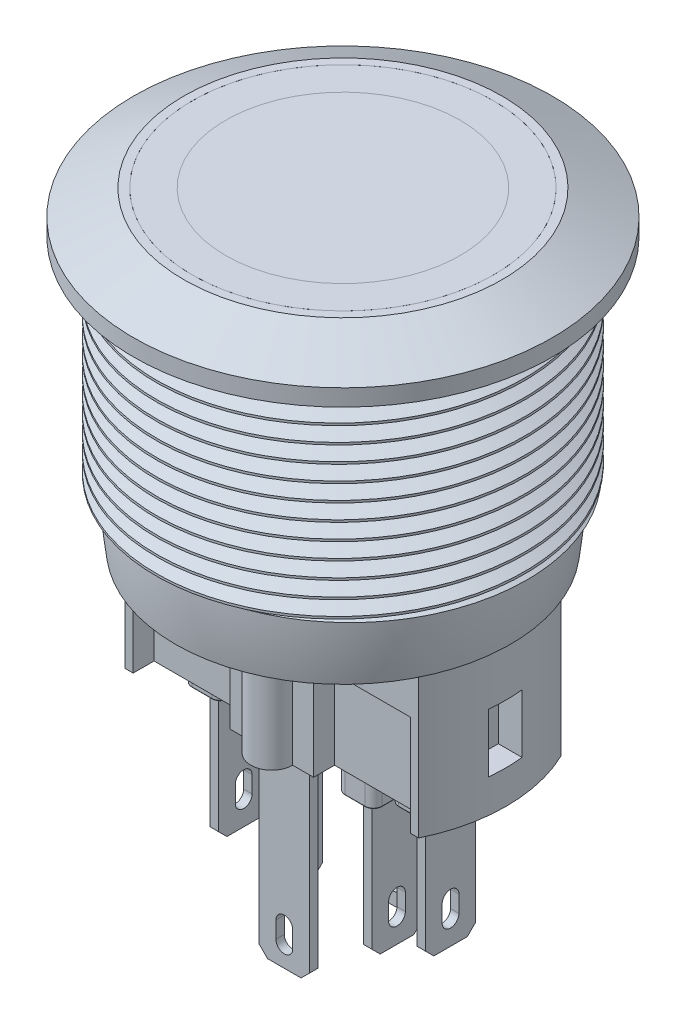
SolidWorks part; units mm, degrees
ref_plane "Ön Düzlem" through (0, 0, 0) normal (0, 0, 1) x (1, 0, 0)
ref_plane "Üst Düzlem" through (0, 0, 0) normal (0, 1, 0) x (1, 0, 0)
ref_plane "Sağ Düzlem" through (0, 0, 0) normal (1, 0, 0) x (0, 0, -1)
sketch "Çizim1" plane through (0, 0, 0) normal (0, 0, 1) x (1, 0, 0)
  line L1 (-11, 3.5267) -> (-11, 16.1)
  line L2 (-11, 16.1) -> (-12.5, 16.1)
  line L3 (-12.5, 16.1) -> (-12.5, 17.1)
  line L6 (0, 17.6) -> (0, 3.5267)
  line L7 (-9, 18.6) -> (-9, 17.6)
  line L8 (-9, 17.6) -> (0, 17.6)
  line L9 (0, 3.5267) -> (-10, 3.5267)
  line L10 (-10, 0) -> (-9.7474, 0)
  line L11 (-10.25, 3.5267) -> (-11, 3.5267)
  line L12 (-9.7474, 0) -> (0, 0) construction
  line L13 (-9, 18.6) -> (-9.5, 18.6)
  line L14 (-9.5, 18.6) -> (-12.5, 17.1)
  line L15 (0, 3.5267) -> (0, 0) construction
  arc A0 (-10.25, 3.5267) -> (-10, 0) centre (14.75, 3.5267) ccw
  arc A1 (-10, 3.5267) -> (-9.7474, 0) centre (14.75, 3.5267) ccw
  arc A2 (-10, 3.5267) -> (-9.7525, 0.0353) centre (14.75, 3.5267) ccw construction
  dimension "D9" = 25
  dimension "D1" = 11
  dimension "D2" = 3.5
  dimension "D3" = 1.5
  dimension "D4" = 1
  dimension "D5" = 1
  dimension "D6" = 2.5
  dimension "D7" = 10
  dimension "D8" = 10.25
  dimension "D11" = 10
  dimension "D12" = 18.6
  dimension "D13" = 0.5
  dimension "D10" = 0.25
revolve "Döndür1" add sketch "Çizim1" angle 360 about L15
sketch "Çizim2" plane through (0, 0, 0) normal (0, 0, 1) x (1, 0, 0)
  line L0 (-10, 3.5267) -> (10, 3.5267) construction
  line L1 (-11, 3.5267) -> (11, 3.5267) construction
  line L2 (-9.7474, 0) -> (9.7474, 0) construction
  line L3 (-10.25, 3.5267) -> (10.25, 3.5267) construction
  line L4 (10, 3.5267) -> (0, 3.5267)
  line L5 (0, 3.5267) -> (0, 0.5)
  line L6 (0, 0.5) -> (9.8051, 0.5)
  arc A0 (10, 3.5267) -> (9.8051, 0.5) centre (-24.9923, 4.2602) cw
  dimension "D1" = 35
  dimension "D2" = 0.5
  dimension "D3" = 10
  dimension "D4" = 3.0267
revolve "Döndür2" add sketch "Çizim2" angle 360 about L5
sketch "Çizim3" plane through (0, 0.5, 0) normal (0, -1, 0) x (1, 0, 0)
  line L0 (0, -4.25) -> (0, 4.25) construction
  line L1 (-8.775, 4.25) -> (-1.25, 4.25)
  line L2 (-8.775, -4.25) -> (-1.25, -4.25)
  line L3 (1.25, 4.25) -> (8.775, 4.25)
  line L4 (1.25, -4.25) -> (8.775, -4.25)
  arc A0 (-8.775, 4.25) -> (-8.775, -4.25) centre (0, 0) ccw
  arc A1 (8.775, -4.25) -> (8.775, 4.25) centre (0, 0) ccw
  circle A2 centre (0, 0) radius 5.5 construction
  arc A3 (1.25, 4.25) -> (-1.25, 4.25) centre (0, 4.25) ccw
  arc A4 (-1.25, -4.25) -> (1.25, -4.25) centre (0, -4.25) ccw
  point P6 (0, 0)
  point P9 (0, 4.25)
  point P12 (0, -4.25)
  dimension "D1" = 19.5
  dimension "D3" = 11
  dimension "D2" = 8.5
  dimension "D4" = 7.525
extrude "Yükseklik-Ekstrüzyon1" add sketch "Çizim3" along normal blind 9
sketch "Çizim5" plane through (0, -8.5, 0) normal (0, -1, 0) x (1, 0, 0)
  line L0 (-1.25, 4.25) -> (-8.775, 4.25) construction
  line L1 (-2.5, -3) -> (-1.5, -3)
  line L2 (-8.275, -3) -> (-8.275, 3)
  line L3 (-2.5, 3) -> (-1.5, 3)
  line L4 (8.275, -3) -> (8.275, 3)
  line L5 (-8.275, -3) -> (8.275, 3) construction
  line L6 (-8.275, 3) -> (8.275, -3) construction
  line L8 (-8.275, 3) -> (-8.275, 4.25)
  line L9 (-8.275, 4.25) -> (-2.5, 4.25)
  line L10 (-2.5, 3) -> (-2.5, 4.25)
  line L11 (8.775, 4.25) -> (1.25, 4.25) construction
  line L13 (2.5, 3) -> (2.5, 4.25)
  line L14 (2.5, 4.25) -> (8.275, 4.25)
  line L15 (8.275, 3) -> (8.275, 4.25)
  line L16 (0, 5.5) -> (0, 3) construction
  line L17 (2.5, 4.25) -> (-2.5, 4.25) construction
  line L18 (0, 0) -> (1.3284, 0) construction
  line L19 (-8.275, -4.25) -> (-2.5, -4.25)
  line L20 (-2.5, -3) -> (-2.5, -4.25)
  line L22 (-8.275, -3) -> (-8.275, -4.25)
  line L23 (2.5, -4.25) -> (8.275, -4.25)
  line L24 (8.275, -3) -> (8.275, -4.25)
  line L26 (2.5, -3) -> (2.5, -4.25)
  line L27 (1.5, 3) -> (2.5, 3)
  line L29 (-1.5, 3) -> (-1.5, 3.5)
  line L30 (-1.5, 3.5) -> (1.5, 3.5)
  line L31 (1.5, 3) -> (1.5, 3.5)
  line L32 (1.5, -3) -> (2.5, -3)
  line L33 (1.5, 3) -> (-1.5, 3) construction
  line L34 (-1.5, -3.5) -> (1.5, -3.5)
  line L35 (-1.5, -3.5) -> (-1.5, -3)
  line L37 (1.5, -3.5) -> (1.5, -3)
  arc A0 (1.25, 4.25) -> (-1.25, 4.25) centre (0, 4.25) ccw construction
  point P0 (0, 0)
  point P25 (0, 4.25)
  point P36 (0, -3)
  point P39 (0, 3)
  dimension "D1" = 5
  dimension "D2" = 6
  dimension "D3" = 0.5
  dimension "D4" = 0.5
  dimension "D5" = 3
extrude "Kes-Ekstrüzyon1" cut sketch "Çizim5" against normal offset from surface (6 mm away) 3 up to face at (0, 0.5, 0)
sketch "Çizim6" plane through (0, 0, 0) normal (1, 0, 0) x (0, 0, -1)
  line L1 (-1, -6.5) -> (1, -6.5)
  line L2 (-1, -6.5) -> (-1, -3)
  line L3 (-1, -3) -> (1, -3)
  line L4 (1, -6.5) -> (1, -3)
  dimension "D1" = 1
  dimension "D2" = 1
  dimension "D3" = 3
  dimension "D4" = 3.5
extrude "Kes-Ekstrüzyon2" cut sketch "Çizim6" against normal through all and the other way through all
sketch "Çizim7" plane through (0, -2.5, 0) normal (0, -1, 0) x (-1, 0, 0)
  line L0 (1.5, -3) -> (2.5, -3) construction
  line L1 (8.275, -3) -> (-8.275, -3)
  line L2 (8.275, -3) -> (8.275, 3)
  line L3 (8.275, 3) -> (-8.275, 3)
  line L4 (-8.275, -3) -> (-8.275, 3)
  line L5 (2.5, 3) -> (1.5, 3) construction
  line L6 (8.275, -4.25) -> (8.275, 4.25) construction
  line L7 (-8.275, 4.25) -> (-8.275, -4.25) construction
extrude "Yükseklik-Ekstrüzyon2" add sketch "Çizim7" along normal up to surface (6 mm away) separate body up to face at (-8.7687, -8.5, 0)
sketch "Çizim8" plane through (0, -8.5, 0) normal (0, -1, 0) x (1, 0, 0)
  line L0 (-6.175, 0) -> (0, 0) construction
  line L1 (-6.775, -2.25) -> (-5.575, -2.25)
  line L2 (-7.275, -1.75) -> (-7.275, 1.75)
  line L3 (-6.775, 2.25) -> (-5.575, 2.25)
  line L4 (-5.075, -1.75) -> (-5.075, 1.75)
  line L5 (-7.275, -2.25) -> (-5.075, 2.25) construction
  line L6 (-7.275, 2.25) -> (-5.075, -2.25) construction
  line L7 (0, 0) -> (0, 2.1485) construction
  line L8 (6.425, -1.5) -> (5.925, -1.5)
  line L9 (-6.425, -1.5) -> (-5.925, -1.5)
  line L10 (-6.425, -1.5) -> (-6.425, 1.5)
  line L11 (-6.425, 1.5) -> (-5.925, 1.5)
  line L12 (-5.925, -1.5) -> (-5.925, 1.5)
  line L13 (-6.425, -1.5) -> (-5.925, 1.5) construction
  line L14 (-6.425, 1.5) -> (-5.925, -1.5) construction
  line L15 (6.425, -1.5) -> (6.425, 1.5)
  line L16 (5.925, -1.5) -> (5.925, 1.5)
  line L17 (6.425, 1.5) -> (5.925, 1.5)
  line L18 (6.775, 2.25) -> (5.575, 2.25)
  line L19 (5.075, -1.75) -> (5.075, 1.75)
  line L20 (6.775, -2.25) -> (5.575, -2.25)
  line L21 (7.275, -1.75) -> (7.275, 1.75)
  line L22 (-8.275, 3) -> (-8.275, -3) construction
  arc A0 (5.075, -1.75) -> (5.575, -2.25) centre (5.575, -1.75) ccw
  arc A1 (6.775, -2.25) -> (7.275, -1.75) centre (6.775, -1.75) ccw
  arc A2 (6.775, 2.25) -> (7.275, 1.75) centre (6.775, 1.75) cw
  arc A3 (5.575, 2.25) -> (5.075, 1.75) centre (5.575, 1.75) ccw
  arc A4 (-6.775, -2.25) -> (-7.275, -1.75) centre (-6.775, -1.75) cw
  arc A5 (-5.575, -2.25) -> (-5.075, -1.75) centre (-5.575, -1.75) ccw
  arc A6 (-5.575, 2.25) -> (-5.075, 1.75) centre (-5.575, 1.75) cw
  arc A7 (-7.275, 1.75) -> (-6.775, 2.25) centre (-6.775, 1.75) cw
  point P0 (-6.175, 0)
  point P25 (5.075, -2.25)
  point P28 (7.275, -2.25)
  point P31 (7.275, 2.25)
  point P34 (5.075, 2.25)
  dimension "D6" = 0.5
  dimension "D1" = 2.2
  dimension "D2" = 4.5
  dimension "D3" = 0.5
  dimension "D4" = 3
  dimension "D5" = 1
extrude "Yükseklik-Ekstrüzyon3" add sketch "Çizim8" along normal blind 1
sketch "Çizim9" plane through (0, -8.5, 0) normal (0, -1, 0) x (1, 0, 0)
  line L1 (-3.575, -2.25) -> (-2.375, -2.25)
  line L2 (-4.075, -1.75) -> (-4.075, 1.75)
  line L3 (-3.575, 2.25) -> (-2.375, 2.25)
  line L4 (-1.875, -1.75) -> (-1.875, 1.75)
  line L5 (-4.075, -2.25) -> (-1.875, 2.25) construction
  line L6 (-4.075, 2.25) -> (-1.875, -2.25) construction
  line L7 (-5.575, 2.25) -> (-6.775, 2.25) construction
  line L8 (-6.775, -2.25) -> (-5.575, -2.25) construction
  line L9 (-5.925, 1.5) -> (-6.425, 1.5) construction
  line L10 (-3.225, -1.5) -> (-2.725, -1.5)
  line L11 (-3.225, -1.5) -> (-3.225, 1.5)
  line L12 (-3.225, 1.5) -> (-2.725, 1.5)
  line L13 (-2.725, -1.5) -> (-2.725, 1.5)
  line L14 (-3.225, -1.5) -> (-2.725, 1.5) construction
  line L15 (-3.225, 1.5) -> (-2.725, -1.5) construction
  line L16 (-2.975, 0) -> (0, 0) construction
  line L17 (0, 0) -> (0, 1.2456) construction
  line L18 (3.225, 1.5) -> (2.725, 1.5)
  line L19 (2.725, -1.5) -> (2.725, 1.5)
  line L20 (3.225, -1.5) -> (2.725, -1.5)
  line L21 (3.225, -1.5) -> (3.225, 1.5)
  line L22 (3.575, 2.25) -> (2.375, 2.25)
  line L23 (1.875, -1.75) -> (1.875, 1.75)
  line L24 (3.575, -2.25) -> (2.375, -2.25)
  line L25 (4.075, -1.75) -> (4.075, 1.75)
  line L26 (-5.075, -1.75) -> (-5.075, 1.75) construction
  arc A0 (1.875, -1.75) -> (2.375, -2.25) centre (2.375, -1.75) ccw
  arc A1 (3.575, -2.25) -> (4.075, -1.75) centre (3.575, -1.75) ccw
  arc A2 (3.575, 2.25) -> (4.075, 1.75) centre (3.575, 1.75) cw
  arc A3 (2.375, 2.25) -> (1.875, 1.75) centre (2.375, 1.75) ccw
  arc A4 (-3.575, -2.25) -> (-4.075, -1.75) centre (-3.575, -1.75) cw
  arc A5 (-2.375, -2.25) -> (-1.875, -1.75) centre (-2.375, -1.75) ccw
  arc A6 (-2.375, 2.25) -> (-1.875, 1.75) centre (-2.375, 1.75) cw
  arc A7 (-4.075, 1.75) -> (-3.575, 2.25) centre (-3.575, 1.75) cw
  point P0 (-2.975, 0)
  point P11 (-2.975, 0)
  point P32 (1.875, -2.25)
  point P35 (4.075, -2.25)
  point P38 (4.075, 2.25)
  point P41 (1.875, 2.25)
  dimension "D4" = 0.5
  dimension "D1" = 1
  dimension "D2" = 2.2
  dimension "D3" = 0.5
extrude "Yükseklik-Ekstrüzyon4" add sketch "Çizim9" along normal offset from surface (2 mm away) 1 up to face at (-6.175, -9.5, 0) offset beyond the face yes
sketch "Çizim10" plane through (0, -9.5, 0) normal (0, -1, 0) x (1, 0, 0)
  line L0 (-6.775, -2.15) -> (-5.575, -2.15)
  line L1 (-5.175, -1.75) -> (-5.175, 1.75)
  line L2 (-5.575, 2.15) -> (-6.775, 2.15)
  line L3 (-7.175, 1.75) -> (-7.175, -1.75)
  line L4 (-6.775, -2.25) -> (-5.575, -2.25)
  line L5 (-5.075, -1.75) -> (-5.075, 1.75)
  line L6 (-5.575, 2.25) -> (-6.775, 2.25)
  line L7 (-7.275, 1.75) -> (-7.275, -1.75)
  line L8 (-6.775, -2.25) -> (-5.575, -2.25) construction
  line L9 (-5.075, -1.75) -> (-5.075, 1.75) construction
  line L10 (-5.575, 2.25) -> (-6.775, 2.25) construction
  line L11 (-7.275, 1.75) -> (-7.275, -1.75) construction
  line L12 (5.575, -2.25) -> (6.775, -2.25)
  line L13 (7.275, -1.75) -> (7.275, 1.75)
  line L14 (6.775, 2.25) -> (5.575, 2.25)
  line L15 (5.075, 1.75) -> (5.075, -1.75)
  line L16 (5.575, -2.25) -> (6.775, -2.25) construction
  line L17 (7.275, -1.75) -> (7.275, 1.75) construction
  line L18 (6.775, 2.25) -> (5.575, 2.25) construction
  line L19 (5.075, 1.75) -> (5.075, -1.75) construction
  line L20 (5.575, -2.15) -> (6.775, -2.15)
  line L21 (7.175, -1.75) -> (7.175, 1.75)
  line L22 (6.775, 2.15) -> (5.575, 2.15)
  line L23 (5.175, 1.75) -> (5.175, -1.75)
  line L25 (-6.425, 1.5) -> (-5.925, 1.5)
  line L26 (-6.425, 1.5) -> (-6.425, -1.5)
  line L27 (-6.425, -1.5) -> (-5.925, -1.5)
  line L28 (-5.925, 1.5) -> (-5.925, -1.5)
  line L29 (5.925, 1.5) -> (6.425, 1.5)
  line L30 (5.925, 1.5) -> (5.925, -1.5)
  line L31 (5.925, -1.5) -> (6.425, -1.5)
  line L32 (6.425, 1.5) -> (6.425, -1.5)
  arc A0 (-5.575, -2.15) -> (-5.175, -1.75) centre (-5.575, -1.75) ccw
  arc A1 (-5.175, 1.75) -> (-5.575, 2.15) centre (-5.575, 1.75) ccw
  arc A2 (-6.775, 2.15) -> (-7.175, 1.75) centre (-6.775, 1.75) ccw
  arc A3 (-7.175, -1.75) -> (-6.775, -2.15) centre (-6.775, -1.75) ccw
  arc A4 (-7.275, -1.75) -> (-6.775, -2.25) centre (-6.775, -1.75) ccw
  arc A5 (-5.575, -2.25) -> (-5.075, -1.75) centre (-5.575, -1.75) ccw
  arc A6 (-5.075, 1.75) -> (-5.575, 2.25) centre (-5.575, 1.75) ccw
  arc A7 (-6.775, 2.25) -> (-7.275, 1.75) centre (-6.775, 1.75) ccw
  arc A8 (-7.275, -1.75) -> (-6.775, -2.25) centre (-6.775, -1.75) ccw construction
  arc A9 (-5.575, -2.25) -> (-5.075, -1.75) centre (-5.575, -1.75) ccw construction
  arc A10 (-5.075, 1.75) -> (-5.575, 2.25) centre (-5.575, 1.75) ccw construction
  arc A11 (-6.775, 2.25) -> (-7.275, 1.75) centre (-6.775, 1.75) ccw construction
  arc A12 (5.075, -1.75) -> (5.575, -2.25) centre (5.575, -1.75) ccw
  arc A13 (6.775, -2.25) -> (7.275, -1.75) centre (6.775, -1.75) ccw
  arc A14 (7.275, 1.75) -> (6.775, 2.25) centre (6.775, 1.75) ccw
  arc A15 (5.575, 2.25) -> (5.075, 1.75) centre (5.575, 1.75) ccw
  arc A16 (5.075, -1.75) -> (5.575, -2.25) centre (5.575, -1.75) ccw construction
  arc A17 (6.775, -2.25) -> (7.275, -1.75) centre (6.775, -1.75) ccw construction
  arc A18 (7.275, 1.75) -> (6.775, 2.25) centre (6.775, 1.75) ccw construction
  arc A19 (5.575, 2.25) -> (5.075, 1.75) centre (5.575, 1.75) ccw construction
  arc A20 (6.775, -2.15) -> (7.175, -1.75) centre (6.775, -1.75) ccw
  arc A21 (7.175, 1.75) -> (6.775, 2.15) centre (6.775, 1.75) ccw
  arc A22 (5.575, 2.15) -> (5.175, 1.75) centre (5.575, 1.75) ccw
  arc A23 (5.175, -1.75) -> (5.575, -2.15) centre (5.575, -1.75) ccw
  dimension "D1" = 0
  dimension "D2" = 0
  dimension "D3" = 0.1
extrude "Kes-Ekstrüzyon3" cut sketch "Çizim10" against normal blind 0.2
sketch "Çizim11" plane through (0, -10.5, 0) normal (0, -1, 0) x (1, 0, 0)
  line L0 (3.225, -1.5) -> (3.225, 1.5) construction
  line L1 (3.225, 1.5) -> (2.725, 1.5) construction
  line L2 (2.725, 1.5) -> (2.725, -1.5) construction
  line L3 (2.725, -1.5) -> (3.225, -1.5) construction
  line L4 (-2.725, -1.5) -> (-2.725, 1.5) construction
  line L5 (-2.725, 1.5) -> (-3.225, 1.5) construction
  line L6 (-3.225, 1.5) -> (-3.225, -1.5) construction
  line L7 (-3.225, -1.5) -> (-2.725, -1.5) construction
  line L8 (3.225, -1.5) -> (3.225, 1.5)
  line L9 (3.225, 1.5) -> (2.725, 1.5)
  line L10 (2.725, 1.5) -> (2.725, -1.5)
  line L11 (2.725, -1.5) -> (3.225, -1.5)
  line L12 (-2.725, -1.5) -> (-2.725, 1.5)
  line L13 (-2.725, 1.5) -> (-3.225, 1.5)
  line L14 (-3.225, 1.5) -> (-3.225, -1.5)
  line L15 (-3.225, -1.5) -> (-2.725, -1.5)
  line L16 (2.375, -2.25) -> (3.575, -2.25) construction
  line L17 (4.075, -1.75) -> (4.075, 1.75) construction
  line L18 (3.575, 2.25) -> (2.375, 2.25) construction
  line L19 (1.875, 1.75) -> (1.875, -1.75) construction
  line L20 (-3.575, -2.25) -> (-2.375, -2.25) construction
  line L21 (-1.875, -1.75) -> (-1.875, 1.75) construction
  line L22 (-2.375, 2.25) -> (-3.575, 2.25) construction
  line L23 (-4.075, 1.75) -> (-4.075, -1.75) construction
  line L24 (2.375, -2.25) -> (3.575, -2.25) construction
  line L25 (4.075, -1.75) -> (4.075, 1.75) construction
  line L26 (3.575, 2.25) -> (2.375, 2.25) construction
  line L27 (1.875, 1.75) -> (1.875, -1.75) construction
  line L28 (-3.575, -2.25) -> (-2.375, -2.25) construction
  line L29 (-1.875, -1.75) -> (-1.875, 1.75) construction
  line L30 (-2.375, 2.25) -> (-3.575, 2.25) construction
  line L31 (-4.075, 1.75) -> (-4.075, -1.75) construction
  line L32 (-3.575, -2.15) -> (-2.375, -2.15)
  line L33 (-1.975, -1.75) -> (-1.975, 1.75)
  line L34 (-2.375, 2.15) -> (-3.575, 2.15)
  line L35 (-3.975, 1.75) -> (-3.975, -1.75)
  line L36 (2.375, -2.15) -> (3.575, -2.15)
  line L37 (3.975, -1.75) -> (3.975, 1.75)
  line L38 (3.575, 2.15) -> (2.375, 2.15)
  line L39 (1.975, 1.75) -> (1.975, -1.75)
  arc A0 (3.575, -2.25) -> (4.075, -1.75) centre (3.575, -1.75) ccw construction
  arc A1 (4.075, 1.75) -> (3.575, 2.25) centre (3.575, 1.75) ccw construction
  arc A2 (2.375, 2.25) -> (1.875, 1.75) centre (2.375, 1.75) ccw construction
  arc A3 (1.875, -1.75) -> (2.375, -2.25) centre (2.375, -1.75) ccw construction
  arc A4 (-2.375, -2.25) -> (-1.875, -1.75) centre (-2.375, -1.75) ccw construction
  arc A5 (-1.875, 1.75) -> (-2.375, 2.25) centre (-2.375, 1.75) ccw construction
  arc A6 (-3.575, 2.25) -> (-4.075, 1.75) centre (-3.575, 1.75) ccw construction
  arc A7 (-4.075, -1.75) -> (-3.575, -2.25) centre (-3.575, -1.75) ccw construction
  arc A8 (3.575, -2.25) -> (4.075, -1.75) centre (3.575, -1.75) ccw construction
  arc A9 (4.075, 1.75) -> (3.575, 2.25) centre (3.575, 1.75) ccw construction
  arc A10 (2.375, 2.25) -> (1.875, 1.75) centre (2.375, 1.75) ccw construction
  arc A11 (1.875, -1.75) -> (2.375, -2.25) centre (2.375, -1.75) ccw construction
  arc A12 (-2.375, -2.25) -> (-1.875, -1.75) centre (-2.375, -1.75) ccw construction
  arc A13 (-1.875, 1.75) -> (-2.375, 2.25) centre (-2.375, 1.75) ccw construction
  arc A14 (-3.575, 2.25) -> (-4.075, 1.75) centre (-3.575, 1.75) ccw construction
  arc A15 (-4.075, -1.75) -> (-3.575, -2.25) centre (-3.575, -1.75) ccw construction
  arc A16 (-2.375, -2.15) -> (-1.975, -1.75) centre (-2.375, -1.75) ccw
  arc A17 (-1.975, 1.75) -> (-2.375, 2.15) centre (-2.375, 1.75) ccw
  arc A18 (-3.575, 2.15) -> (-3.975, 1.75) centre (-3.575, 1.75) ccw
  arc A19 (-3.975, -1.75) -> (-3.575, -2.15) centre (-3.575, -1.75) ccw
  arc A20 (3.575, -2.15) -> (3.975, -1.75) centre (3.575, -1.75) ccw
  arc A21 (3.975, 1.75) -> (3.575, 2.15) centre (3.575, 1.75) ccw
  arc A22 (2.375, 2.15) -> (1.975, 1.75) centre (2.375, 1.75) ccw
  arc A23 (1.975, -1.75) -> (2.375, -2.15) centre (2.375, -1.75) ccw
  dimension "D1" = 0.1
extrude "Kes-Ekstrüzyon4" cut sketch "Çizim11" against normal blind 0.2
fillet "Radyus1" radius 0.05 96 edges at (7.0578, -9.3, 2.0328) (7.175, -9.3, 0) (7.0578, -9.3, -2.0328) (6.175, -9.3, -2.15) (5.2921, -9.3, -2.0328) (5.175, -9.3, 0) (5.2921, -9.3, 2.0328) (3.8578, -10.3, 2.0328) (3.975, -10.3, 0) (3.8578, -10.3, -2.0328) (2.975, -10.3, -2.15) (2.0921, -10.3, -2.0328) (1.975, -10.3, 0) (2.0921, -10.3, 2.0328) (-2.0921, -10.3, 2.0328) (-1.975, -10.3, 0) (-2.0921, -10.3, -2.0328) (-2.975, -10.3, -2.15) (-3.8578, -10.3, -2.0328) (-3.975, -10.3, 0) (-3.8578, -10.3, 2.0328) (-5.2921, -9.3, 2.0328) (-5.175, -9.3, 0) (-5.2921, -9.3, -2.0328) (-6.175, -9.3, -2.15) (-7.0578, -9.3, -2.0328) (-7.175, -9.3, 0) (-7.0578, -9.3, 2.0328) (6.175, -9.3, 2.15) (2.975, -10.3, 2.15) (-2.975, -10.3, 2.15) (-6.175, -9.3, 2.15) (7.1285, -9.5, 2.1036) (7.275, -9.5, 0) (7.1285, -9.5, -2.1036) (6.175, -9.5, -2.25) (5.2214, -9.5, -2.1036) (5.075, -9.5, 0) (5.2214, -9.5, 2.1036) (7.0578, -9.5, 2.0328) (7.175, -9.5, 0) (7.0578, -9.5, -2.0328) (6.175, -9.5, -2.15) (5.2921, -9.5, -2.0328) (5.175, -9.5, 0) (5.2921, -9.5, 2.0328) (2.0214, -10.5, 2.1036) (1.875, -10.5, 0) (2.0214, -10.5, -2.1036) (2.975, -10.5, -2.25) (3.9285, -10.5, -2.1036) (4.075, -10.5, 0) (3.9285, -10.5, 2.1036) (3.8578, -10.5, 2.0328) (3.975, -10.5, 0) (3.8578, -10.5, -2.0328) (2.975, -10.5, -2.15) (2.0921, -10.5, -2.0328) (1.975, -10.5, 0) (2.0921, -10.5, 2.0328) (-3.9285, -10.5, 2.1036) (-4.075, -10.5, 0) (-3.9285, -10.5, -2.1036) (-2.975, -10.5, -2.25) (-2.0214, -10.5, -2.1036) (-1.875, -10.5, 0) (-2.0214, -10.5, 2.1036) (-2.0921, -10.5, 2.0328) (-1.975, -10.5, 0) (-2.0921, -10.5, -2.0328) (-2.975, -10.5, -2.15) (-3.8578, -10.5, -2.0328) (-3.975, -10.5, 0) (-3.8578, -10.5, 2.0328) (-5.2214, -9.5, 2.1036) (-5.075, -9.5, 0) (-5.2214, -9.5, -2.1036) (-6.175, -9.5, -2.25) (-7.1285, -9.5, -2.1036) (-7.275, -9.5, 0) (-7.1285, -9.5, 2.1036) (-5.2921, -9.5, 2.0328) (-5.175, -9.5, 0) (-5.2921, -9.5, -2.0328) (-6.175, -9.5, -2.15) (-7.0578, -9.5, -2.0328) (-7.175, -9.5, 0) (-7.0578, -9.5, 2.0328) (6.175, -9.5, 2.25) (6.175, -9.5, 2.15) (2.975, -10.5, 2.25) (2.975, -10.5, 2.15) (-2.975, -10.5, 2.25) (-2.975, -10.5, 2.15) (-6.175, -9.5, 2.25) (-6.175, -9.5, 2.15)
sketch "Çizim12" plane through (0, -8.5, 0) normal (0, -1, 0) x (1, 0, 0)
  line L4 (-5.925, -1.5) -> (-5.925, 1.5)
  line L5 (-5.925, 1.5) -> (-6.425, 1.5)
  line L6 (-6.425, 1.5) -> (-6.425, -1.5)
  line L7 (-6.425, -1.5) -> (-5.925, -1.5)
  line L8 (-5.925, -1.5) -> (-5.925, 1.5)
  line L9 (-5.925, 1.5) -> (-6.425, 1.5)
  line L10 (-6.425, 1.5) -> (-6.425, -1.5)
  line L11 (-6.425, -1.5) -> (-5.925, -1.5)
  line L12 (6.425, -1.5) -> (6.425, 1.5)
  line L13 (6.425, 1.5) -> (5.925, 1.5)
  line L14 (5.925, 1.5) -> (5.925, -1.5)
  line L15 (5.925, -1.5) -> (6.425, -1.5)
  line L16 (6.425, -1.5) -> (6.425, 1.5)
  line L17 (6.425, 1.5) -> (5.925, 1.5)
  line L18 (5.925, 1.5) -> (5.925, -1.5)
  line L19 (5.925, -1.5) -> (6.425, -1.5)
  dimension "D1" = 0
  dimension "D2" = 0
extrude "Yükseklik-Ekstrüzyon5" add sketch "Çizim12" along normal offset from surface (8.9 mm away) 36 up to face at (-9.5, 18.6, 0)
sketch "Çizim13" plane through (0, 0, 0) normal (1, 0, 0) x (0, 0, -1)
  line L0 (0, -9.45) -> (0, -17.4) construction
  line L5 (1.75, -9.45) -> (-1.75, -9.45) construction
  line L6 (1.5, -17.4) -> (-1.5, -17.4) construction
  line L7 (0, -15.95) -> (0, -14.95) construction
  line L8 (-0.5, -15.95) -> (-0.5, -14.95)
  line L9 (0.5, -15.95) -> (0.5, -14.95)
  arc A0 (-0.5, -15.95) -> (0.5, -15.95) centre (0, -15.95) ccw
  arc A1 (0.5, -14.95) -> (-0.5, -14.95) centre (0, -14.95) ccw
  point P8 (0, -15.45)
  dimension "D1" = 0.5
  dimension "D2" = 1
  dimension "D3" = 6
extrude "Kes-Ekstrüzyon5" cut sketch "Çizim13" against normal through all and the other way through all
sketch "Çizim14" plane through (0, -8.5, 0) normal (0, -1, 0) x (1, 0, 0)
  line L4 (3.225, -1.5) -> (3.225, 1.5)
  line L5 (3.225, 1.5) -> (2.725, 1.5)
  line L6 (2.725, 1.5) -> (2.725, -1.5)
  line L7 (2.725, -1.5) -> (3.225, -1.5)
  line L8 (3.225, -1.5) -> (3.225, 1.5)
  line L9 (3.225, 1.5) -> (2.725, 1.5)
  line L10 (2.725, 1.5) -> (2.725, -1.5)
  line L11 (2.725, -1.5) -> (3.225, -1.5)
  line L12 (-2.725, -1.5) -> (-2.725, 1.5)
  line L13 (-2.725, 1.5) -> (-3.225, 1.5)
  line L14 (-3.225, 1.5) -> (-3.225, -1.5)
  line L15 (-3.225, -1.5) -> (-2.725, -1.5)
  line L16 (-2.725, -1.5) -> (-2.725, 1.5)
  line L17 (-2.725, 1.5) -> (-3.225, 1.5)
  line L18 (-3.225, 1.5) -> (-3.225, -1.5)
  line L19 (-3.225, -1.5) -> (-2.725, -1.5)
  dimension "D1" = 0
  dimension "D2" = 0
extrude "Yükseklik-Ekstrüzyon6" add sketch "Çizim14" along normal offset from surface (10.4 mm away) 37.5 up to face at (-9.5, 18.6, 0)
sketch "Çizim15" plane through (-2.725, 0, 0) normal (1, 0, 0) x (0, 0, -1)
  line L0 (0, -16.45) -> (0, -17.45) construction
  line L1 (0.5, -16.45) -> (0.5, -17.45)
  line L2 (-0.5, -16.45) -> (-0.5, -17.45)
  line L3 (0, -15.95) -> (0, -16.45) construction
  arc A0 (0.5, -16.45) -> (-0.5, -16.45) centre (0, -16.45) ccw
  arc A1 (-0.5, -17.45) -> (0.5, -17.45) centre (0, -17.45) ccw
  point P3 (0, -16.95)
  dimension "D1" = 0.5
  dimension "D2" = 1
  dimension "D3" = 0.5
extrude "Kes-Ekstrüzyon6" cut sketch "Çizim15" against normal up to vertex (0.5 mm away) and the other way up to vertex (5.9499 mm away) up to point (-3.225, -18.9, 1.5) other way up to point (3.225, -10.3, 1.5)
sketch "Çizim16" plane through (0, -2.5, 0) normal (0, -1, 0) x (1, 0, 0)
  line L4 (-1.5, 3) -> (1.5, 3)
  line L5 (1.5, 3) -> (1.5, 3.5)
  line L6 (1.5, 3.5) -> (-1.5, 3.5)
  line L7 (-1.5, 3.5) -> (-1.5, 3)
  line L8 (-1.5, 3) -> (1.5, 3)
  line L9 (1.5, 3) -> (1.5, 3.5)
  line L10 (1.5, 3.5) -> (-1.5, 3.5)
  line L11 (-1.5, 3.5) -> (-1.5, 3)
  line L12 (1.5, -3) -> (-1.5, -3)
  line L13 (-1.5, -3) -> (-1.5, -3.5)
  line L14 (-1.5, -3.5) -> (1.5, -3.5)
  line L15 (1.5, -3.5) -> (1.5, -3)
  line L16 (1.5, -3) -> (-1.5, -3)
  line L17 (-1.5, -3) -> (-1.5, -3.5)
  line L18 (-1.5, -3.5) -> (1.5, -3.5)
  line L19 (1.5, -3.5) -> (1.5, -3)
  dimension "D1" = 0
  dimension "D2" = 0
extrude "Yükseklik-Ekstrüzyon7" add sketch "Çizim16" along normal offset from surface (17.5 mm away) 38.6 up to face at (-9.5, 18.6, 0)
sketch "Çizim18" plane through (0, 0, 3.5) normal (0, 0, 1) x (1, 0, 0)
  line L0 (0, -20) -> (0, -18.75) construction
  line L1 (-1.5, -20) -> (1.5, -20) construction
  line L2 (0, -18.75) -> (0, -17.75) construction
  line L3 (-0.5, -18.75) -> (-0.5, -17.75)
  line L4 (0.5, -18.75) -> (0.5, -17.75)
  arc A0 (-0.5, -18.75) -> (0.5, -18.75) centre (0, -18.75) ccw
  arc A1 (0.5, -17.75) -> (-0.5, -17.75) centre (0, -17.75) ccw
  point P5 (0, -18.25)
  dimension "D2" = 0.5
  dimension "D1" = 1.25
  dimension "D3" = 1
extrude "Kes-Ekstrüzyon7" cut sketch "Çizim18" against normal up to vertex (7 mm away) up to point (-1.5, -20, -3.5)
chamfer "Pah1" distance 0.5 angle 45 12 edges at (-1.5, -20, 3.25) (1.5, -20, 3.25) (6.175, -17.4, 1.5) (6.175, -17.4, -1.5) (2.975, -18.9, 1.5) (2.975, -18.9, -1.5) (-2.975, -18.9, -1.5) (-2.975, -18.9, 1.5) (-6.175, -17.4, 1.5) (-6.175, -17.4, -1.5) (-1.5, -20, -3.25) (1.5, -20, -3.25)
sketch "Çizim19" plane through (0, 0, 0) normal (0, 0, 1) x (1, 0, 0)
  line L0 (9, 18.6) -> (-9, 18.6) construction
  line L1 (9, 18.6) -> (7, 18.6)
  line L2 (9, 18.6) -> (9, 17.6)
  line L3 (9, 17.6) -> (7, 17.6)
  line L4 (7, 18.6) -> (7, 17.6)
  line L5 (9.5, 18.6) -> (-9.5, 18.6) construction
  line L6 (9, 17.6) -> (-9, 17.6) construction
  line L8 (0, 0) -> (0, 21.5003) construction
  dimension "D1" = 2
  dimension "D2" = 9
revolve "Döndür3" add sketch "Çizim19" angle 360 about L8
sketch "Çizim20" plane through (0, 0, 0) normal (0, 0, 1) x (1, 0, 0)
  line L0 (7, 18.6) -> (-7, 18.6) construction
  line L2 (0, 17.6) -> (0, 18.6)
  line L3 (0, 18.6) -> (7, 18.6)
  line L4 (7, 17.6) -> (7, 18.6)
  line L5 (7, 17.6) -> (0, 17.6)
  line L6 (-7, 17.6) -> (7, 17.6) construction
  line L7 (0, 0) -> (0, 17.6) construction
  dimension "D1" = 7
revolve "Döndür4" add sketch "Çizim20" angle 360 about L7
sketch "Çizim21" plane through (0, 3.5267, 0) normal (0, -1, 0) x (1, 0, 0)
  circle A0 centre (0, 0) radius 11 construction
  circle A1 centre (0, 0) radius 11
curve "Helis/Spiral1" pitch 1 height 11.75 radius 11 centre (0, 3.5267, 0) axis (0, 1, 0) start towards (0, 0, 1)
sketch "Çizim22" plane through (0, 0, 0) normal (1, 0, 0) x (0, 0, -1)
  line L1 (-10.25, 3.5267) -> (-11.375, 4.1762)
  line L2 (-11.375, 4.1762) -> (-11.375, 2.8772)
  line L3 (-11.375, 2.8772) -> (-10.25, 3.5267)
  circle A0 centre (-11, 3.5267) radius 0.375 construction
sweep "Kes-Süpür1" cut profiles "Çizim22" path "Helis/Spiral1" align with end faces yes
